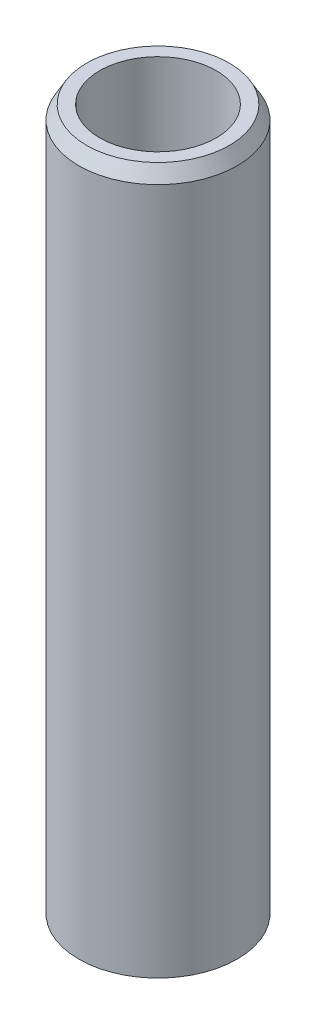
SolidWorks part; units mm, degrees
ref_plane "Front Plane" through (0, 0, 0) normal (0, 0, 1) x (1, 0, 0)
ref_plane "Top Plane" through (0, 0, 0) normal (0, 1, 0) x (1, 0, 0)
ref_plane "Right Plane" through (0, 0, 0) normal (1, 0, 0) x (0, 0, -1)
sketch "Sketch1" plane through (0, 0, 0) normal (0, 1, 0) x (1, 0, 0)
  circle A0 centre (0, 0) radius 20
  dimension "SHAFT_OD" = 40
extrude "Boss-Extrude1" add sketch "Sketch1" along normal blind 178.8795
sketch "Sketch2" plane through (0, 0, 0) normal (0, 1, 0) x (1, 0, 0)
  circle A0 centre (0, 0) radius 14.7159
  dimension "BORE_D" = 29.4319
extrude "Cut-Extrude1" cut sketch "Sketch2" along normal through all
chamfer "Chamfer1" distance 3.4436 angle 30 2 edges at (0, 178.8795, 20) (0, 0, 20) first distance on face at (0, 178.8795, 20) first distance on face at (0, 0, 14.7159)
